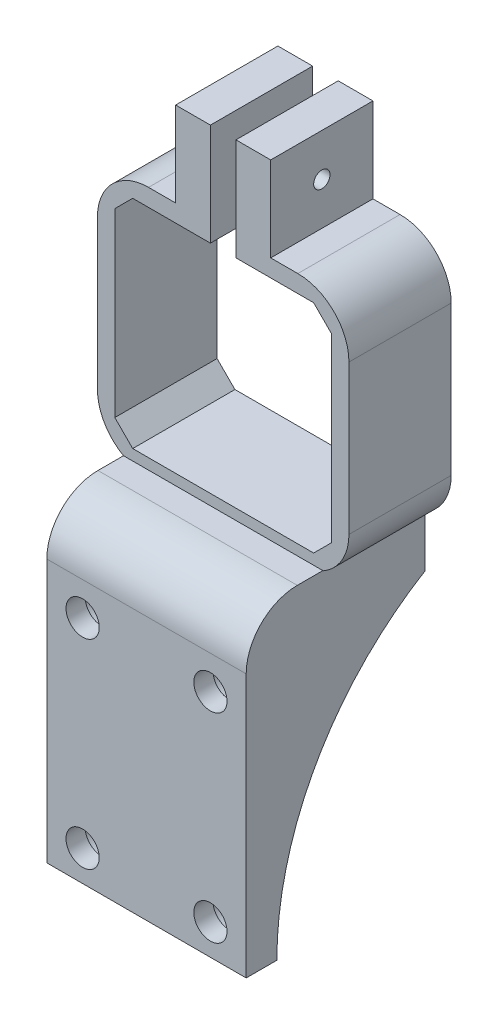
SolidWorks part; units mm, degrees
ref_plane "Front Plane" through (0, 0, 0) normal (0, 0, 1) x (1, 0, 0)
ref_plane "Top Plane" through (0, 0, 0) normal (0, 1, 0) x (1, 0, 0)
ref_plane "Right Plane" through (0, 0, 0) normal (1, 0, 0) x (0, 0, -1)
sketch "Sketch1" plane through (0, 0, 0) normal (0, 0, 1) x (1, 0, 0)
  line L1 (-21.2, -21.2) -> (21.2, -21.2)
  line L2 (-21.2, -21.2) -> (-21.2, 21.2)
  line L3 (-21.2, 21.2) -> (21.2, 21.2)
  line L4 (21.2, -21.2) -> (21.2, 21.2)
  line L5 (-21.2, -21.2) -> (21.2, 21.2) construction
  line L6 (-21.2, 21.2) -> (21.2, -21.2) construction
  line L7 (-24.6, -24.6) -> (24.6, -24.6)
  line L8 (-24.6, -24.6) -> (-24.6, 24.6)
  line L9 (-24.6, 24.6) -> (24.6, 24.6)
  line L10 (24.6, -24.6) -> (24.6, 24.6)
  line L11 (-24.6, -24.6) -> (24.6, 24.6) construction
  line L12 (-24.6, 24.6) -> (24.6, -24.6) construction
  point P0 (0, 0)
  point P5 (0, 0)
  dimension "D1" = 42.4
  dimension "D2" = 42.4
  dimension "D3" = 49.2
  dimension "D4" = 49.2
extrude "Boss-Extrude1" add sketch "Sketch1" along normal mid plane 20
chamfer "Chamfer1" distance 3.5 angle 45 4 edges at (21.2, -21.2, 0) (-21.2, -21.2, 0) (-21.2, 21.2, 0) (21.2, 21.2, 0)
fillet "Fillet1" radius 10 4 edges at (24.6, -24.6, 0) (-24.6, -24.6, 0) (-24.6, 24.6, 0) (24.6, 24.6, 0)
sketch "Sketch2" plane through (0, 0, 10) normal (0, 0, 1) x (1, 0, 0)
  line L5 (17.7, 21.2) -> (-17.7, 21.2) construction
  line L11 (-9.3, 17.8) -> (9.3, 17.8)
  line L12 (-9.3, 17.8) -> (-9.3, 24.6)
  line L17 (-9.3, 24.6) -> (9.3, 24.6)
  line L18 (9.3, 17.8) -> (9.3, 24.6)
  line L23 (-9.3, 17.8) -> (9.3, 24.6) construction
  line L24 (-9.3, 24.6) -> (9.3, 17.8) construction
  point P0 (0, 21.2)
  dimension "D1" = 6.8
  dimension "D2" = 18.6
extrude "Cut-Extrude1" cut sketch "Sketch2" against normal up to next
sketch "Sketch4" plane through (0, 21.2, 0) normal (0, -1, 0) x (1, 0, 0)
  line L1 (-9.3, -10) -> (-2.5, -10)
  line L2 (-9.3, -10) -> (-9.3, 10)
  line L3 (-9.3, 10) -> (-2.5, 10)
  line L4 (-2.5, -10) -> (-2.5, 10)
  line L5 (-17.7, 10) -> (17.7, 10) construction
  line L7 (9.3, -10) -> (2.5, -10)
  line L8 (9.3, -10) -> (9.3, 10)
  line L9 (9.3, 10) -> (2.5, 10)
  line L10 (2.5, -10) -> (2.5, 10)
  dimension "D1" = 20
  dimension "D2" = 6.8
  dimension "D3" = 20
  dimension "D4" = 6.8
extrude "Boss-Extrude2" add sketch "Sketch4" against normal blind 20
sketch "Sketch5" plane through (9.3, 0, 0) normal (1, 0, 0) x (0, 0, -1)
  circle A0 centre (0, 32.9) radius 1.6
  dimension "D1" = 3.2
extrude "Cut-Extrude2" cut sketch "Sketch5" against normal through all
sketch "Sketch7" plane through (0, 0, 0) normal (0, 0, 1) x (1, 0, 0)
  line L0 (0, 9.494) -> (0, -58.694) construction
  line L6 (-19.5, -24.6) -> (-19.5, -84.8)
  line L7 (-19.5, -84.8) -> (19.5, -84.8)
  line L8 (19.5, -84.8) -> (19.5, -24.6)
  line L10 (-19.5, -24.6) -> (-19.5, -23.3172)
  line L11 (-19.5, -23.3172) -> (19.5, -23.2738)
  line L12 (19.5, -23.2738) -> (19.5, -24.6)
  arc A1 (-24.6, -14.6) -> (-14.6, -24.6) centre (-14.6, -14.6) ccw construction
  dimension "D1" = 39
  dimension "D3" = 60.2
extrude "Boss-Extrude3" add sketch "Sketch7" along normal blind 25
sketch "Sketch8" plane through (0, 0, 0) normal (0, 0, -1) x (-1, 0, 0)
  line L3 (-19.5, -23.3172) -> (19.5, -23.3172)
  line L4 (-19.5, -23.3172) -> (-19.5, -33.3172)
  line L5 (-19.5, -33.3172) -> (19.5, -33.3172)
  line L6 (19.5, -23.3172) -> (19.5, -33.3172)
  line L7 (19.5, -23.3172) -> (19.5, -84.8) construction
  arc A1 (-24.6, -14.6) -> (-14.6, -24.6) centre (-14.6, -14.6) ccw construction
  dimension "D1" = 10
  dimension "D2" = 39
extrude "Boss-Extrude4" add sketch "Sketch8" along normal blind 10
sketch "Sketch9" plane through (0, 0, 25) normal (0, 0, 1) x (1, 0, 0)
  line L1 (-19.5, -84.8) -> (19.5, -84.8) construction
  line L2 (-19.5, -84.8) -> (-19.5, -33.8) construction
  line L3 (-19.5, -33.8) -> (19.5, -33.8) construction
  line L4 (19.5, -84.8) -> (19.5, -33.8) construction
  line L5 (19.5, -84.8) -> (19.5, -23.2738) construction
  dimension "D1" = 51
  dimension "D2" = 39
fillet "Fillet3" radius 10 1 edges at (0, -23.2955, 25)
sketch "Sketch10" plane through (-19.5, 0, 0) normal (-1, 0, 0) x (0, 0, 1)
  line L0 (0, -33.3172) -> (25, -33.3172) construction
  line L1 (25, -84.8) -> (25, -33.8) construction
  line L7 (0, -84.8) -> (19, -84.8)
  line L8 (0, -84.8) -> (0, -33.3172)
  line L9 (0, -33.3172) -> (19, -33.3172)
  line L10 (19, -84.8) -> (19, -33.3172)
  dimension "D1" = 51.4828
  dimension "D2" = 19
  dimension "D3" = 25
extrude "Cut-Extrude3" cut sketch "Sketch10" against normal up to next
fillet "Fillet4" radius 60 1 edges at (0, -33.3172, 19)
sketch "Sketch11" plane through (0, 0, 25) normal (0, 0, 1) x (1, 0, 0)
  line L0 (-19.5, -84.8) -> (-19.5, -33.8) construction
  line L1 (-19.5, -33.8) -> (19.5, -33.8) construction
  line L2 (19.5, -84.8) -> (19.5, -33.8) construction
  line L3 (-19.5, -84.8) -> (19.5, -84.8) construction
  circle A0 centre (-12.5, -39.8) radius 3.25
  circle A1 centre (12.5, -39.8) radius 3.25
  circle A2 centre (-12.5, -78.8) radius 3.25
  circle A3 centre (12.5, -78.8) radius 3.25
  dimension "D1" = 6.5
  dimension "D2" = 7
  dimension "D3" = 6
  dimension "D4" = 7
  dimension "D5" = 6
extrude "Cut-Extrude4" cut sketch "Sketch11" against normal through all
sketch "Sketch15" plane through (0, 0, -10) normal (0, 0, -1) x (-1, 0, 0)
  circle A0 centre (-12.5, -39.8) radius 4.5
  circle A1 centre (12.5, -39.8) radius 4.5
  dimension "D1" = 9
  dimension "D2" = 9
extrude "Cut-Extrude6" cut sketch "Sketch15" against normal blind 31.25
sketch "Sketch16" plane through (0, 0, -10) normal (0, 0, -1) x (-1, 0, 0)
  circle A0 centre (-12.5, -78.8) radius 4.5
  circle A1 centre (12.5, -78.8) radius 4.5
  dimension "D1" = 9
  dimension "D2" = 9
extrude "Cut-Extrude7" cut sketch "Sketch16" against normal blind 31.25
